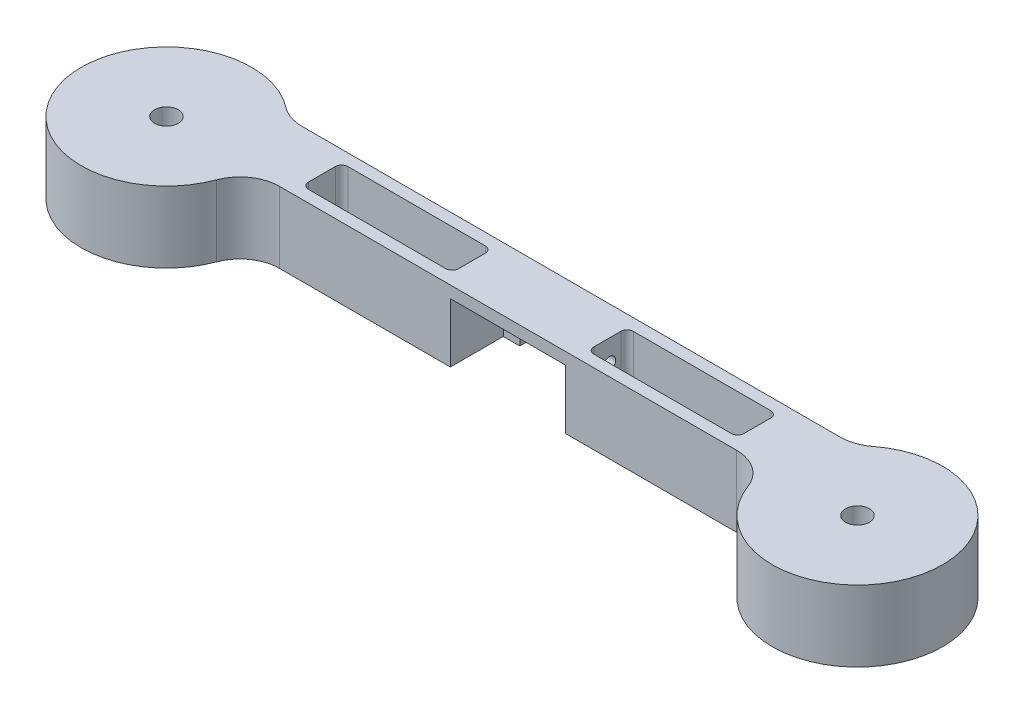
SolidWorks part; units mm, degrees
note: The reader was unsure of these and kept them because the rebuilt part matched: shared geometry of "Sketch1<3>".
material "6061 Alloy"
ref_plane "Front Plane" through (0, 0, 0) normal (0, 0, 1) x (1, 0, 0)
ref_plane "Top Plane" through (0, 0, 0) normal (0, 1, 0) x (1, 0, 0)
ref_plane "Right Plane" through (0, 0, 0) normal (1, 0, 0) x (0, 0, -1)
sketch "Sketch1" plane through (0, 0, 0) normal (0, 1, 0) x (1, 0, 0)
  line L0 (-10.033, 21.1341) -> (126.3443, 21.1341)
  line L1 (-29.3444, 6.1341) -> (145.6556, 6.1341) construction
  line L2 (0.2686, 5.1341) -> (116.0426, 5.1341)
  circle A0 centre (-29.3444, 6.1341) radius 19.05
  circle A1 centre (145.6556, 6.1341) radius 19.05
  arc A2 (-16.1462, 23.2202) -> (-9.1056, -1.3837) centre (-29.3444, 6.1341) ccw
  arc A3 (125.4168, -1.3837) -> (132.4574, 23.2202) centre (145.6556, 6.1341) ccw
  circle A4 centre (-29.3444, 6.1341) radius 3
  circle A5 centre (145.6556, 6.1341) radius 3
  arc A6 (-16.1462, 23.2202) -> (-10.033, 21.1341) centre (-10.033, 31.1341) ccw
  arc A7 (-9.1056, -1.3837) -> (0.2686, 5.1341) centre (0.2686, -4.8659) cw
  arc A8 (125.4168, -1.3837) -> (116.0426, 5.1341) centre (116.0426, -4.8659) ccw
  arc A9 (132.4574, 23.2202) -> (126.3443, 21.1341) centre (126.3443, 31.1341) cw
  point P18 (58.1556, 6.1341)
  dimension "D4" = 38.1
  dimension "D1" = 2.54
  dimension "D3" = 6
  dimension "D6" = 10
  dimension "D2" = 175
  dimension "D5" = 15
  dimension "D7" = 1
extrude "Extrude1" add sketch "Sketch1" along normal blind 18
extrude "Extrude2" cut sketch "Sketch1<3>" along normal blind 10
sketch "Sketch1<3>" plane through (0, 0, 0) normal (0, 1, 0) x (1, 0, 0) same geometry as "Sketch1"
sketch "Sketch2" plane through (0, 0, -21.1341) normal (0, 0, -1) x (-1, 0, 0)
  line L0 (-47.6106, 7.04) -> (-68.7006, 7.04) construction
  line L1 (-68.5424, 7.04) -> (-68.7006, 7.04)
  line L2 (-58.1556, 0) -> (-58.1556, 7.04) construction
  line L3 (10.033, 0) -> (-126.3443, 0) construction
  circle A0 centre (-68.5424, 7.04) radius 1.52
  circle A1 centre (-47.6106, 7.04) radius 1.52
  dimension "D3" = 3.04
  dimension "D1" = 21.09
  dimension "D2" = 7.04
extrude "Extrude3" cut sketch "Sketch2" against normal through all
sketch "Sketch3" plane through (0, 0, -21.1341) normal (0, 0, -1) x (-1, 0, 0)
  line L0 (-72.7606, 15) -> (-43.5506, 15)
  line L1 (10.033, 18) -> (-126.3443, 18) construction
  line L2 (-58.1556, 0) -> (-58.1556, 15) construction
  line L3 (10.033, 0) -> (-126.3443, 0) construction
  line L4 (-72.7606, 15) -> (-72.7606, 0)
  line L5 (-43.5506, 15) -> (-43.5506, 0)
  line L6 (-43.5506, 0) -> (-72.7606, 0)
  dimension "D1" = 29.21
  dimension "D2" = 3
extrude "Extrude4" cut sketch "Sketch3" against normal through all from offset 2.6
sketch "Sketch6" plane through (0, 18, 0) normal (0, 1, 0) x (1, 0, 0)
  line L0 (58.1556, 5.1341) -> (58.1556, 21.1341) construction
  line L1 (0.2686, 5.1341) -> (116.0426, 5.1341) construction
  line L2 (-10.033, 21.1341) -> (126.3443, 21.1341) construction
  line L3 (41.0106, 13.1341) -> (58.1556, 13.1341) construction
  line L4 (41.0106, 13.1341) -> (41.0106, 16.5466)
  line L5 (39.4231, 18.1341) -> (4.5981, 18.1341)
  line L6 (3.0106, 16.5466) -> (3.0106, 9.7216)
  line L7 (4.5981, 8.1341) -> (39.4231, 8.1341)
  line L8 (41.0106, 9.7216) -> (41.0106, 13.1341)
  line L9 (75.3006, 9.7216) -> (75.3006, 13.1341)
  line L10 (111.7131, 8.1341) -> (76.8881, 8.1341)
  line L11 (113.3006, 16.5466) -> (113.3006, 9.7216)
  line L12 (76.8881, 18.1341) -> (111.7131, 18.1341)
  line L13 (75.3006, 13.1341) -> (75.3006, 16.5466)
  arc A0 (39.4231, 18.1341) -> (41.0106, 16.5466) centre (39.4231, 16.5466) cw
  arc A1 (3.0106, 16.5466) -> (4.5981, 18.1341) centre (4.5981, 16.5466) cw
  arc A2 (4.5981, 8.1341) -> (3.0106, 9.7216) centre (4.5981, 9.7216) cw
  arc A3 (41.0106, 9.7216) -> (39.4231, 8.1341) centre (39.4231, 9.7216) cw
  arc A4 (75.3006, 9.7216) -> (76.8881, 8.1341) centre (76.8881, 9.7216) ccw
  arc A5 (111.7131, 8.1341) -> (113.3006, 9.7216) centre (111.7131, 9.7216) ccw
  arc A6 (113.3006, 16.5466) -> (111.7131, 18.1341) centre (111.7131, 16.5466) ccw
  arc A7 (76.8881, 18.1341) -> (75.3006, 16.5466) centre (76.8881, 16.5466) ccw
  point P14 (41.0106, 18.1341)
  point P17 (3.0106, 18.1341)
  point P20 (3.0106, 8.1341)
  point P36 (113.3006, 8.1341)
  point P37 (113.3006, 18.1341)
  point P38 (75.3006, 18.1341)
  dimension "D5" = 1.5875
  dimension "D1" = 17.145
  dimension "D2" = 5
  dimension "D3" = 10
  dimension "D4" = 38
extrude "Extrude6" cut sketch "Sketch6" against normal blind 10
sketch "Sketch8" plane through (75.3006, 0, 0) normal (1, 0, 0) x (0, 0, -1)
  line L0 (16.5466, 18) -> (9.7216, 18) construction
  line L2 (16.5466, 8) -> (16.5466, 18) construction
  circle A0 centre (13.6966, 12.37) radius 1.53
  dimension "D1" = 3.06
  dimension "D3" = 2.85
  dimension "D2" = 5.63
extrude "Extrude7" cut sketch "Sketch8" against normal blind 43
sketch "Sketch9" plane through (0, 0, -21.1341) normal (0, 0, -1) x (-1, 0, 0)
  circle A0 centre (-47.6106, 7.04) radius 1.52 construction
  circle A1 centre (-58.0765, -0.1101) radius 11.1551 construction
  circle A4 centre (-58.0765, -0.1101) radius 9.59 construction
  circle A5 centre (-68.5424, 7.04) radius 1.52 construction
  circle A6 centre (-58.0765, -0.1101) radius 10.352
  line M3 (-126.3443, 0) -> (10.033, 0)
  dimension "D1" = 20.704
  dimension "D2" = 19.18
extrude "Extrude8" cut sketch "Sketch9" against normal through all contours A6 M3
